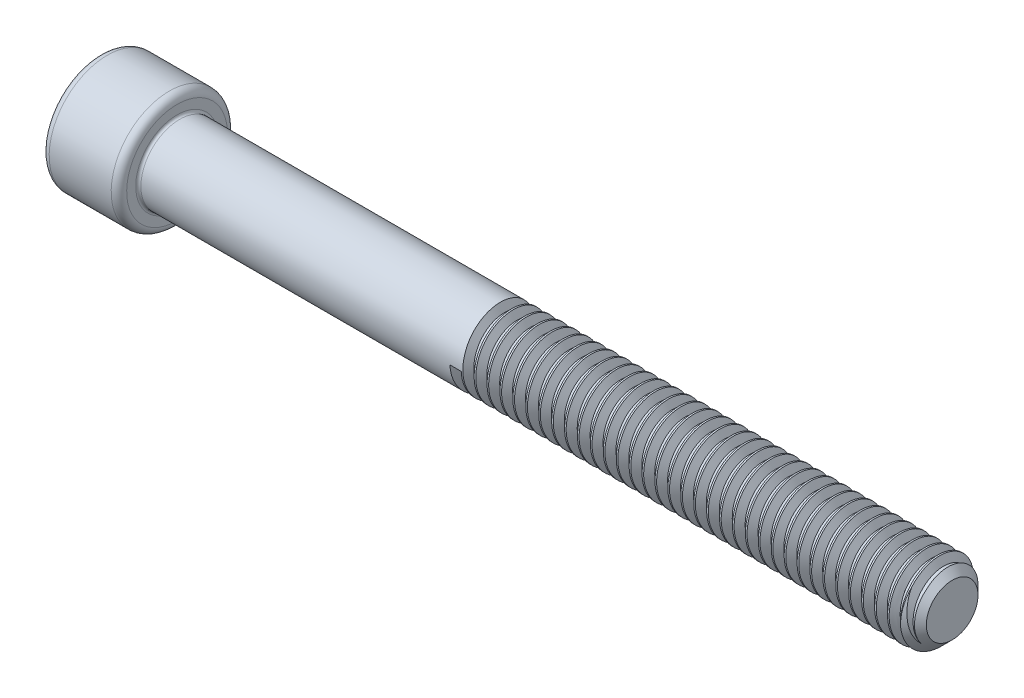
SolidWorks part; units mm, degrees
ref_plane "Front" through (0, 0, 0) normal (0, 0, 1) x (1, 0, 0)
ref_plane "Top" through (0, 0, 0) normal (0, 1, 0) x (1, 0, 0)
ref_plane "Right" through (0, 0, 0) normal (1, 0, 0) x (0, 0, -1)
sketch "Sketch1" plane through (0, 0, 0) normal (0, 0, 1) x (1, 0, 0)
  line L0 (0, 0) -> (33, 0) construction
  line L1 (0, 0) -> (0, 1.95)
  line L2 (0.3, 2.25) -> (2.7, 2.25)
  line L3 (3, 1.95) -> (3, 1.6)
  line L4 (3.1, 1.5) -> (32.5, 1.5)
  line L5 (32.5, 1.5) -> (33, 1)
  line L6 (33, 1) -> (33, 0)
  line L7 (33, 0) -> (0, 0)
  arc A0 (3, 1.6) -> (3.1, 1.5) centre (3.1, 1.6) ccw
  arc A1 (0.3, 2.25) -> (0, 1.95) centre (0.3, 1.95) ccw
  arc A2 (3, 1.95) -> (2.7, 2.25) centre (2.7, 1.95) ccw
  point P12 (0, 2.25)
  point P15 (3, 2.25)
  dimension "D7" = 0.1
  dimension "D8" = 0.3
  dimension "D9" = 0.3
  dimension "D1" = 1.5
  dimension "D2" = 0.5
  dimension "D3" = 0.5
  dimension "D4" = 30
  dimension "D5" = 2.25
  dimension "D6" = 3
revolve "Revolve1" add sketch "Sketch1" angle 360 about L0
sketch "Sketch4" plane through (0, 0, 0) normal (0, 1, 0) x (1, 0, 0)
  line L0 (0, 0) -> (33, 0) construction
  line L1 (33, -1) -> (33, 1) construction
sketch "Sketch2" plane through (0, 0, 0) normal (-1, 0, 0) x (0, 0, 1)
  line L1 (1.4434, 0) -> (0.7217, 1.25)
  line L2 (0.7217, 1.25) -> (-0.7217, 1.25)
  line L3 (-0.7217, 1.25) -> (-1.4434, 0)
  line L4 (-1.4434, 0) -> (-0.7217, -1.25)
  line L5 (-0.7217, -1.25) -> (0.7217, -1.25)
  line L6 (0.7217, -1.25) -> (1.4434, 0)
  circle A0 centre (0, 0) radius 1.25 construction
  dimension "D1" = 2.5
extrude "Cut-Extrude1" cut sketch "Sketch2" against normal blind 3
sketch "Sketch3" plane through (0, 0, 0) normal (0, 1, 0) x (1, 0, 0)
  line L0 (3, 1.4434) -> (3, 0)
  line L1 (3, 0) -> (3.8333, 0)
  line L2 (3.8333, 0) -> (3, 1.4434)
  dimension "D1" = 60
revolve "Cut-Revolve1" cut sketch "Sketch3" angle 360 about L0
thread "Thread1" pitch 0.5 method cut trim with start face yes profile "Thread Profile2" start angle 0, offset 1, length 18, pitch 0.5, diameter 3
ref_plane "Plane2" through (33.5, 0, 1.5) normal (0, -1, 0) x (0, 0, 1)
sketch "Thread Profile2" plane through (33.5, 0, 1.5) normal (0, -1, 0) x (0, 0, 1)
  line L0 (0, 0) -> (0, 0.5) construction
  line L11 (0, 0) -> (0, 0.4375)
  line L12 (0, 0.4375) -> (-0.2706, 0.2812)
  line L13 (-0.2706, 0.2812) -> (-0.2706, 0.1562)
  line L15 (-0.2706, 0.1562) -> (0, 0)
  line L17 (-0.2706, 0.2187) -> (0, 0.2187) construction
  point P2 (0, 0)
  dimension "Pitch" = 0.5
  dimension "Profile_Angle" = 60
  dimension "Profile_Land" = 0.125
  dimension "Profile_Height" = 0.2706
